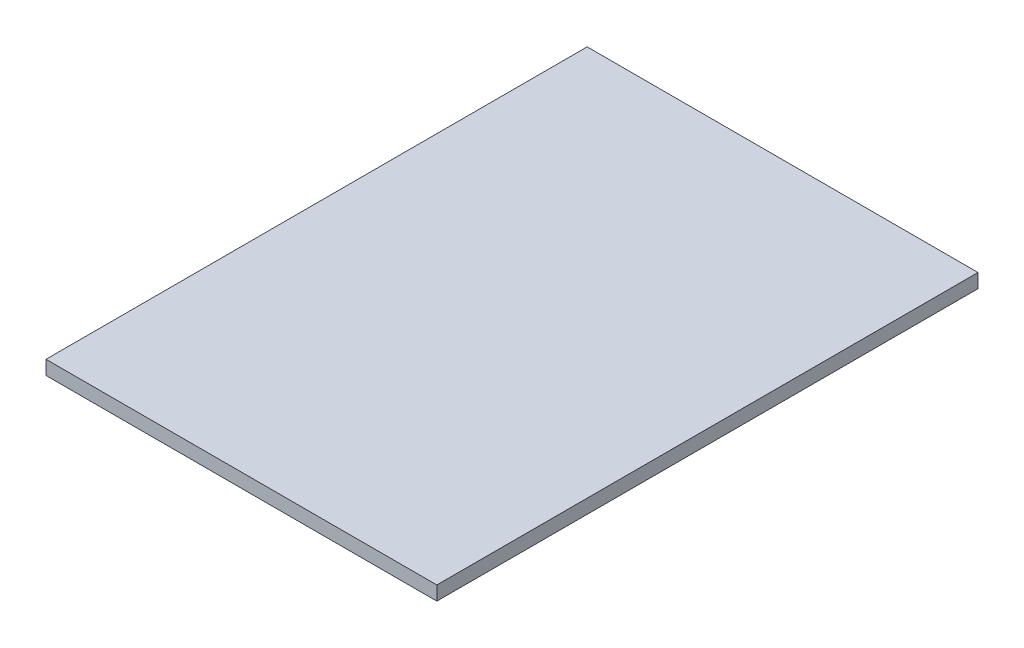
SolidWorks part; units mm, degrees
ref_plane "Front Plane" through (0, 0, 0) normal (0, 0, 1) x (1, 0, 0)
ref_plane "Top Plane" through (0, 0, 0) normal (0, 1, 0) x (1, 0, 0)
ref_plane "Right Plane" through (0, 0, 0) normal (1, 0, 0) x (0, 0, -1)
sketch "Sketch1" plane through (0, 0, 0) normal (0, 1, 0) x (1, 0, 0)
  line L0 (-24.765, 34.29) -> (24.765, 34.29)
  line L1 (-25.4, -34.925) -> (25.4, -34.925) construction
  line L2 (-25.4, -34.925) -> (-25.4, 34.925) construction
  line L3 (-25.4, 34.925) -> (25.4, 34.925) construction
  line L4 (25.4, -34.925) -> (25.4, 34.925) construction
  line L5 (-25.4, -34.925) -> (25.4, 34.925) construction
  line L6 (-25.4, 34.925) -> (25.4, -34.925) construction
  line L7 (24.765, -34.29) -> (24.765, 34.29)
  line L8 (-24.765, -34.29) -> (24.765, -34.29)
  line L9 (-24.765, -34.29) -> (-24.765, 34.29)
  point P0 (0, 0)
  dimension "D1" = 50.8
  dimension "D2" = 69.85
  dimension "D3" = 0.635
extrude "Boss-Extrude1" add sketch "Sketch1" along normal blind 1.778
